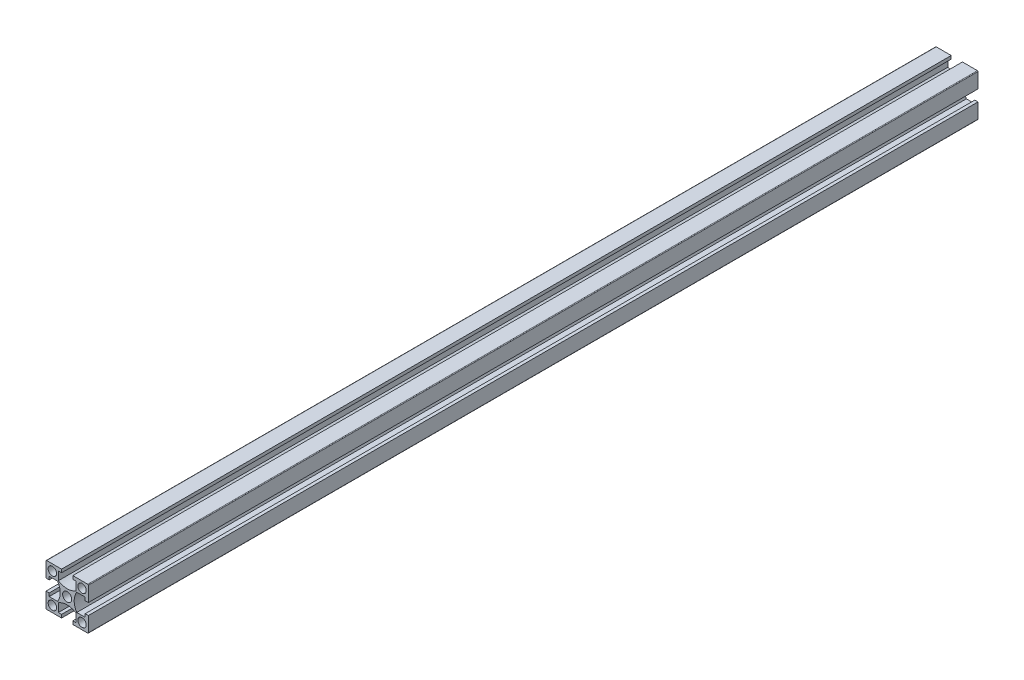
SolidWorks part; units mm, degrees
material "3.0255 (EN-AW 1350A)"
ref_plane "정면" through (0, 0, 0) normal (0, 0, 1) x (1, 0, 0)
ref_plane "윗면" through (0, 0, 0) normal (0, 1, 0) x (1, 0, 0)
ref_plane "우측면" through (0, 0, 0) normal (1, 0, 0) x (0, 0, -1)
sketch "스케치1" plane through (0, 0, 0) normal (0, 0, 1) x (1, 0, 0)
  line L0 (0, 32.0265) -> (0, -31.6588) construction
  line L1 (-10, 10) -> (-10, -10)
  line L2 (-10, 10) -> (10, 10)
  line L3 (-10, 2.65) -> (-8.5, 2.65)
  line L4 (13.6618, 0) -> (-11.6993, 0) construction
  line L5 (-8.5, 2.65) -> (-8.5, 4.15)
  line L6 (-8.5, 4.15) -> (-4.5032, 4.15)
  line L7 (-10, -2.65) -> (-8.5, -2.65)
  line L8 (-8.5, -2.65) -> (-8.5, -4.15)
  line L9 (-8.5, -4.15) -> (-4.5032, -4.15)
  line L10 (-10, -10) -> (10, -10)
  line L11 (10, 10) -> (10, -10)
  circle A0 centre (-7, 7) radius 2
  circle A1 centre (-7, -7) radius 2
  arc A2 (-4.5032, 4.15) -> (-4.5032, -4.15) centre (-11.0587, 0) cw
  circle A3 centre (0, 0) radius 2.15
  circle A4 centre (7, 7) radius 2
  circle A5 centre (7, -7) radius 2
  point P21 (-10, 0)
  point P23 (-3.3, 0)
  point P31 (0, -10)
  point P32 (0, 10)
  dimension "D3" = 4
  dimension "D9" = 6.7
  dimension "D10" = 4.3
  dimension "D11" = 7.7587
  dimension "D1" = 20
  dimension "D2" = 20
  dimension "D4" = 14
  dimension "D5" = 14
  dimension "D6" = 5.3
  dimension "D7" = 8.3
  dimension "D8" = 1.5
extrude "보스-돌출1" add sketch "스케치1" along normal blind 420 contours A0 | A4 | A3 | A5 | A1 | A2 L6 L5 L3 L1 L7 L8 L9 | L2 L11 L10 L1 region at (-6.6069, 0, 0) region at (-7, 7, 0) region at (-7, -7, 0) region at (0, 0, 0) region at (7, 7, 0) region at (7, -7, 0)
extrude "컷-돌출1" cut sketch "스케치1<3>" along normal up to next contours A2 L6 L5 L3 L1 L7 L8 L9 region at (-6.6069, 0, 0)
sketch "스케치1<3>" plane through (0, 0, 0) normal (0, 0, 1) x (1, 0, 0) same geometry as "스케치1"
pattern_circular "원형 패턴1" count 4 over 360 about axis through (0, 0, 420) along (0, 0, -1) of "컷-돌출1" reverse direction yes
fillet "필렛1" radius 0.3 4 edges at (10, -10, 210) (-10, -10, 210) (-10, 10, 210) (10, 10, 210)
sketch "스케치4" plane through (0, 10, 0) normal (0, 1, 0) x (1, 0, 0)
  line L0 (-4.15, -420) -> (4.15, -420) construction
  line L1 (4.15, 0) -> (-4.15, 0) construction
  circle A0 centre (0, -11) radius 2.5
  circle A1 centre (0, -409) radius 2.5
  dimension "D1" = 11
  dimension "D2" = 11
extrude "컷-돌출2" cut sketch "스케치4" against normal through all
sketch "스케치5" plane through (-10, 0, 0) normal (-1, 0, 0) x (0, 0, 1)
  line L0 (0, -2.65) -> (0, -9.7) construction
  line L1 (420, -4.15) -> (420, 4.15) construction
  circle A0 centre (131, 0) radius 2.5
  circle A1 centre (289, 0) radius 2.5
  dimension "D1" = 131
  dimension "D2" = 131
extrude "컷-돌출3" cut sketch "스케치5" against normal through all
sketch "스케치6" plane through (0, 10, 0) normal (0, 1, 0) x (1, 0, 0)
  line L0 (4.15, 0) -> (-4.15, 0) construction
  line L1 (-4.15, -420) -> (4.15, -420) construction
  circle A0 centre (0, -110) radius 2.5
  circle A1 centre (0, -310) radius 2.5
  dimension "D1" = 110
  dimension "D2" = 110
extrude "컷-돌출4" cut sketch "스케치6" against normal through all
sketch "스케치7" plane through (0, -10, 0) normal (0, -1, 0) x (1, 0, 0)
  line L0 (2.65, 0) -> (9.7, 0) construction
  line L1 (2.65, 420) -> (9.7, 420) construction
  circle A0 centre (0, 249.5) radius 2.5
  circle A1 centre (0, 170.5) radius 2.5
  dimension "D1" = 170.5
  dimension "D2" = 170.5
extrude "컷-돌출5" cut sketch "스케치7" against normal through all
